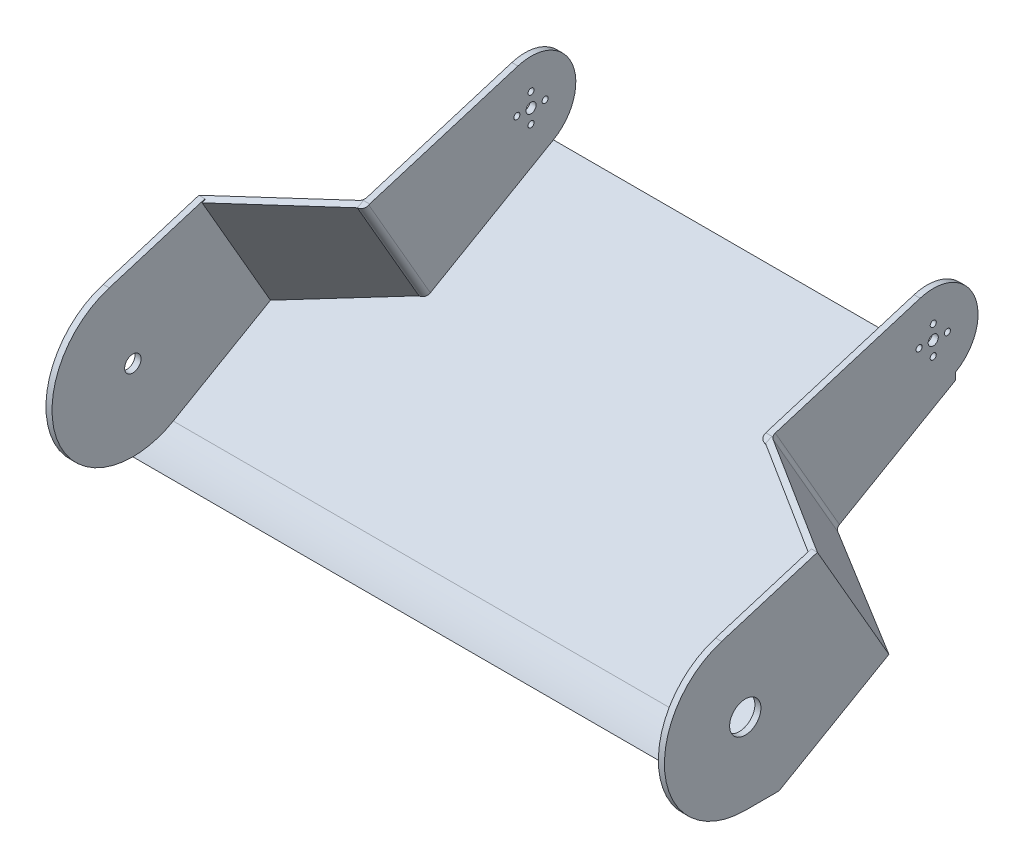
SolidWorks part; units mm, degrees
ref_plane "前视基准面" through (0, 0, 0) normal (0, 0, 1) x (1, 0, 0)
ref_plane "上视基准面" through (0, 0, 0) normal (0, 1, 0) x (1, 0, 0)
ref_plane "右视基准面" through (0, 0, 0) normal (1, 0, 0) x (0, 0, -1)
sketch "草图2" plane through (0, 0, 0) normal (1, 0, 0) x (0, 0, -1)
  line L0 (-11.7006, 38.2504) -> (138.5148, 84.2007)
  line L1 (0, -40) -> (16.7102, -40)
  line L2 (16.7102, -40) -> (120, 19.5373)
  line L3 (156.0716, 43.7921) -> (120, 23)
  line L4 (120, 23) -> (19.9756, -34.6551)
  line L6 (120, 19.5373) -> (156.0716, 40.3294)
  line L7 (156.0716, 43.7921) -> (156.0716, 40.3294)
  circle A0 centre (0, 0) radius 40
  circle A1 centre (145, 63) radius 2.5
  circle A2 centre (145, 63) radius 22.1704
  circle A3 centre (0, 0) radius 3
  circle A4 centre (145, 70) radius 1.5
  circle A5 centre (152, 63) radius 1.5
  circle A6 centre (145, 56) radius 1.5
  circle A7 centre (138, 63) radius 1.5
  point P28 (145, 63)
  dimension "D1" = 80
  dimension "D7" = 5
  dimension "D6" = 44.3408
  dimension "D8" = 6
  dimension "D11" = 3
  dimension "D2" = 120
  dimension "D3" = 23
  dimension "D4" = 25
  dimension "D5" = 40
  dimension "D9" = 3
  dimension "D10" = 16.7102
  dimension "D12" = 7
  dimension "D13" = 4
extrude "凸台-拉伸1" add sketch "草图2" along normal blind 3 contours A0 A3 | A2 A1 | A0 L1 L2 L4 | A2 L0 A0 L4 L3 region at (0, 33.1628, -76.327) region at (0, 31.2466, -23.1176) region at (0, 80.3187, -157.8131) region at (0, 0.2577, -83.4271)
sketch "草图4" plane through (3, 0, 0) normal (1, 0, 0) x (0, 0, -1)
  line L0 (0, -40) -> (16.7102, -40)
  line L1 (16.7102, -40) -> (156.0716, 40.3294)
  line L2 (156.0716, 40.3294) -> (156.0716, 43.7921)
  line L3 (156.0716, 43.7921) -> (19.9756, -34.6551)
  line L4 (156.0716, 43.7921) -> (156.0716, 40.3294) construction
  arc A0 (0, -40) -> (19.9756, -34.6551) centre (0, 0) ccw
extrude "凸台-拉伸2" add sketch "草图4" along normal blind 196
ref_plane "基准面5" through (101, 0, 0) normal (1, 0, 0) x (0, 0, -1)
mirror "镜向2" about plane through (101, 0, 0) normal (1, 0, 0) of "凸台-拉伸1"
sketch "草图5" plane through (202, 0, 0) normal (1, 0, 0) x (0, 0, -1)
  circle A0 centre (0, 0) radius 8
  dimension "D1" = 16
extrude "切除-拉伸1" cut sketch "草图5" against normal blind 10
sketch "草图6" plane through (0, 0, 0) normal (-1, 0, 0) x (0, 0, 1)
  circle A0 centre (0, 0) radius 4.05
  dimension "D1" = 8.1
extrude "切除-拉伸2" cut sketch "草图6" against normal blind 10
ref_plane "基准面3" through (251, 0, 0) normal (1, 0, 0) x (0, 0, -1)
sketch "草图8" plane through (251, 0, 0) normal (1, 0, 0) x (0, 0, -1)
  circle A0 centre (0, 0) radius 40
extrude "凸台-拉伸3" add sketch "草图8" along normal blind 3 separate body
sketch "草图9" plane through (251, 0, 0) normal (1, 0, 0) x (0, 0, -1)
  line L0 (0, -40) -> (16.7102, -40)
  line L1 (0, -40) -> (16.7102, -40) construction
  line L2 (16.7102, -40) -> (53.7479, -18.6511)
  line L3 (16.7102, -40) -> (156.0716, 40.3294) construction
  line L4 (53.7479, -18.6511) -> (52.2498, -16.0519)
  line L5 (156.0716, 43.7921) -> (19.9756, -34.6551) construction
  line L6 (52.2498, -16.0519) -> (19.9756, -34.6551)
  circle A0 centre (0, 0) radius 40 construction
  arc A1 (0, -40) -> (19.9756, -34.6551) centre (0, 0) ccw
extrude "凸台-拉伸4" add sketch "草图9" against normal blind 61 and the other way blind 3
sketch "草图10" plane through (0, -37.2542, -21.4737) normal (0, -0.8664, -0.4994) x (1, 0, 0)
  line L0 (254, -37.2519) -> (254, -57.2519)
  line L2 (254, -57.2519) -> (202, -87.2741)
  line L3 (202, -37.2519) -> (202, -155.3571) construction
  line L4 (202, -87.2741) -> (202, -37.2519)
  line L5 (202, -37.2519) -> (254, -37.2519)
  dimension "D1" = 20
  dimension "D2" = 60
  dimension "D3" = 50.0222
extrude "凸台-拉伸5" add sketch "草图10" against normal blind 3
sketch "草图14" plane through (254, 0, 0) normal (1, 0, 0) x (0, 0, -1)
  line L0 (-11.7006, 38.2504) -> (35.6798, 52.7439)
  line L1 (-11.7006, 38.2504) -> (138.5148, 84.2007) construction
  line L2 (35.6798, 52.7439) -> (69.5773, -6.0641)
  line L3 (69.5773, -6.0641) -> (19.9756, -34.6551)
  line L4 (69.5773, -6.0641) -> (71.0755, -8.6633) construction
  line L5 (16.7102, -40) -> (71.0755, -8.6633) construction
  arc A0 (19.9756, -34.6551) -> (-11.7006, 38.2504) centre (0, 0) ccw
extrude "凸台-拉伸14" add sketch "草图14" against normal blind 3
sketch "草图15" plane through (88.2908, 76.3686, -132.4901) normal (0.5, 0.4325, -0.7503) x (-0.866, 0.2497, -0.4332)
  line L0 (-191.3445, -43) -> (-191.3445, 27.878)
  line L1 (-131.3001, -43) -> (-131.3001, 20.9739)
  line L2 (-170.4548, 38.9825) -> (-93.9096, 3.7768) construction
  line L3 (-131.3001, 20.9739) -> (-191.3445, 27.878)
  line L4 (-191.3445, -43) -> (-131.3001, -43)
extrude "凸台-拉伸15" add sketch "草图15" against normal blind 3
mirror "镜向8" about plane through (101, 0, 0) normal (1, 0, 0) of "凸台-拉伸15"
mirror "镜向10" about plane through (101, 0, 0) normal (1, 0, 0) of "凸台-拉伸5"
mirror "镜向11" about plane through (101, 0, 0) normal (1, 0, 0) of "凸台-拉伸4"
mirror "镜向12" about plane through (101, 0, 0) normal (1, 0, 0) of "凸台-拉伸14"
sketch "草图16" plane through (-52, 0, 0) normal (-1, 0, 0) x (0, 0, 1)
  circle A0 centre (0, 0) radius 40
extrude "凸台-拉伸16" add sketch "草图16" against normal blind 3
sketch "草图17" plane through (202, 0, 0) normal (1, 0, 0) x (0, 0, -1)
  line L0 (-11.1203, 38.4231) -> (61.7391, 60.7153)
  line L1 (62.0375, 60.1977) -> (92.5867, 7.1987)
  line L2 (62.0375, 60.1977) -> (92.5867, 7.1987) construction
  line L3 (92.5867, 7.1987) -> (68.0767, -6.9291) construction
  line L4 (92.5867, 7.1987) -> (19.9756, -34.6551)
  line L5 (65.1382, 61.7551) -> (35.6798, 52.7439) construction
  line L6 (62.0375, 60.1977) -> (65.1382, 61.7551)
  line L7 (65.1382, 61.7551) -> (61.7391, 60.7153)
  arc A0 (-11.1203, 38.4231) -> (19.9756, -34.6551) centre (0, 0) ccw
extrude "切除-拉伸5" cut sketch "草图17" against normal blind 20
sketch "草图18" plane through (0, 38.2504, 11.7006) normal (0, 0.9563, 0.2925) x (1, 0, 0)
  line L0 (199, 76.7989) -> (202, 76.9328)
  line L1 (202, 76.9328) -> (202, 0)
  line L2 (202, 0) -> (199, 0)
  line L3 (199, 0) -> (199, 76.7989)
extrude "切除-拉伸6" cut sketch "草图18" against normal blind 20
sketch "草图21" plane through (3, 0, 0) normal (1, 0, 0) x (0, 0, -1)
  line L0 (92.5867, 7.1987) -> (62.0375, 60.1977)
  line L1 (65.1382, 61.7551) -> (35.6798, 52.7439) construction
  line L2 (61.7391, 60.7153) -> (-11.7006, 38.2504)
  line L3 (92.5867, 7.1987) -> (19.9756, -34.6551)
  line L4 (61.7391, 60.7153) -> (65.1382, 61.7551)
  line L5 (65.1382, 61.7551) -> (138.5148, 84.2007) construction
  line L6 (65.1382, 61.7551) -> (62.0375, 60.1977)
  arc A0 (-11.7006, 38.2504) -> (19.9756, -34.6551) centre (0, 0) ccw
extrude "切除-拉伸7" cut sketch "草图21" along direction (1, 0, 0) on the side against the normal up to next (3 mm away)
fillet "圆角3" radius 3 1 edges at (3, 33.6982, -77.3121) type face fillet first side face at (1.5, 33.6982, -77.3121) second side face at (3, 52.9965, -106.4779)
fillet "圆角4" radius 3 1 edges at (199, 33.6982, -77.3121) type face fillet first side face at (200.5, 33.6982, -77.3121) second side face at (199, 52.9965, -106.4779)
fillet "圆角5" radius 3 1 edges at (202, 34.0423, -81.1121) type face fillet first side face at (202, 63, -147.5) second side face at (228, 28.0413, -67.2449)
fillet "圆角6" radius 3 1 edges at (0, 34.0423, -81.1121) type face fillet first side face at (0, 63, -139.5) second side face at (-26, 28.0413, -67.2449)
sketch "草图22" plane through (254, 0, 0) normal (1, 0, 0) x (0, 0, -1)
  circle A0 centre (0, 0) radius 7.75
  dimension "D1" = 15.5
extrude "切除-拉伸8" cut sketch "草图22" against normal blind 10 contours A0
sketch "草图23" plane through (-52, 0, 0) normal (-1, 0, 0) x (0, 0, 1)
  circle A0 centre (0, 0) radius 4.05
  dimension "D1" = 8.1
extrude "切除-拉伸9" cut sketch "草图23" against normal blind 10
